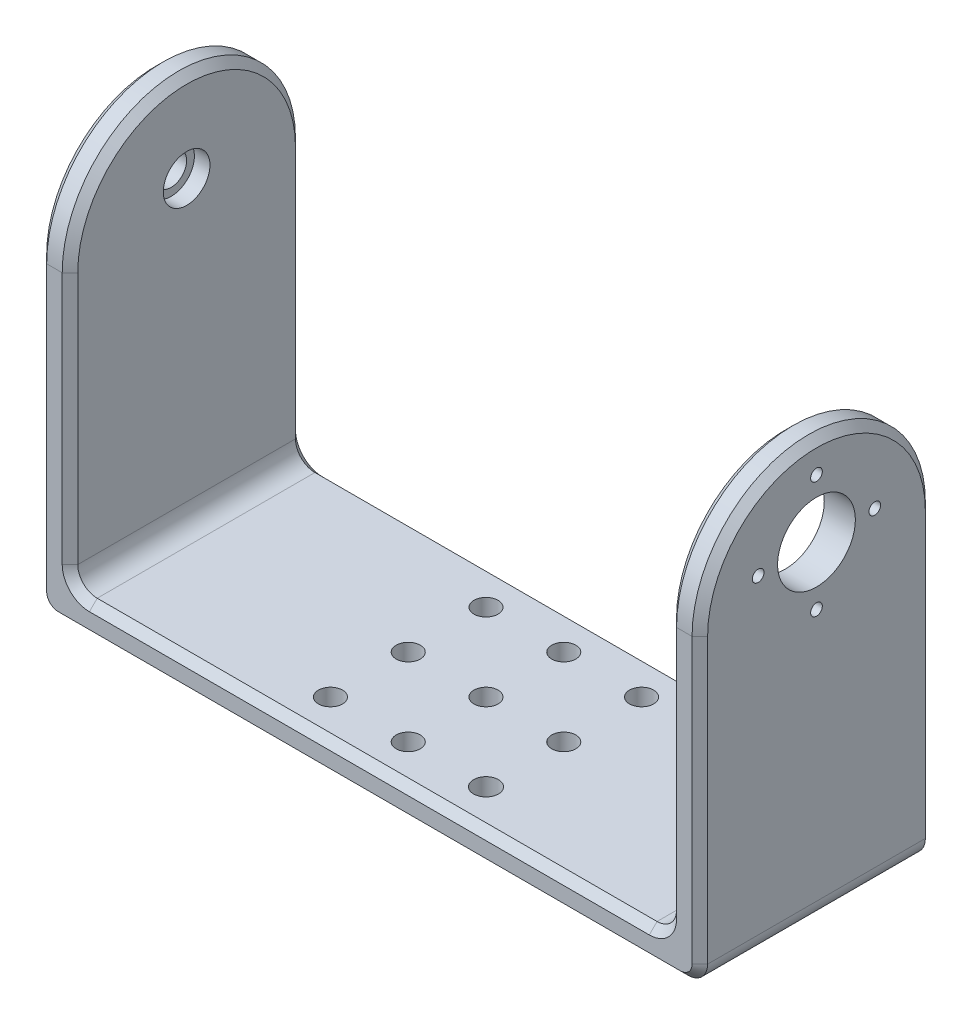
SolidWorks part; units mm, degrees
ref_plane "Front Plane" through (0, 0, 0) normal (0, 0, 1) x (1, 0, 0)
ref_plane "Top Plane" through (0, 0, 0) normal (0, 1, 0) x (1, 0, 0)
ref_plane "Right Plane" through (0, 0, 0) normal (1, 0, 0) x (0, 0, -1)
sketch "Sketch1" plane through (0, 0, 0) normal (0, 1, 0) x (1, 0, 0)
  line L1 (-85, 30) -> (85, 30)
  line L2 (-85, 30) -> (-85, -30)
  line L3 (-85, -30) -> (85, -30)
  line L4 (85, 30) -> (85, -30)
extrude "Boss-Extrude1" add sketch "Sketch1" along normal blind 8
sketch "Sketch2" plane through (0, 8, 0) normal (0, 1, 0) x (1, 0, 0)
  line L1 (-85, 30) -> (-77, 30)
  line L2 (-85, 30) -> (-85, -30)
  line L3 (-85, -30) -> (-77, -30)
  line L4 (-77, 30) -> (-77, -30)
  line L5 (77, 30) -> (77, -30)
  line L6 (85, -30) -> (77, -30)
  line L7 (85, 30) -> (85, -30)
  line L8 (85, 30) -> (77, 30)
extrude "Boss-Extrude2" add sketch "Sketch2" along normal blind 100
sketch "Sketch3" plane through (85, 0, 0) normal (1, 0, 0) x (0, 0, -1)
  circle A0 centre (0, 85) radius 10
  circle A3 centre (0, 70) radius 1.5
  circle A4 centre (0, 100) radius 1.5
  circle A5 centre (-15, 85) radius 1.5
  circle A6 centre (15, 85) radius 1.5
sketch "Sketch4" plane through (-85, 0, 0) normal (-1, 0, 0) x (0, 0, 1)
  circle A0 centre (0, 85) radius 4
extrude "Cut-Extrude1" cut sketch "Sketch3" against normal blind 10
sketch "Sketch5" plane through (-85, 0, 0) normal (-1, 0, 0) x (0, 0, 1)
  circle A0 centre (0, 85) radius 5
extrude "Boss-Extrude3" add sketch "Sketch5" along normal blind 1.5
sketch "Sketch6" plane through (-86.5, 0, 0) normal (-1, 0, 0) x (0, 0, 1)
  circle A0 centre (0, 85) radius 4
extrude "Cut-Extrude3" cut sketch "Sketch6" against normal blind 15
sketch "Sketch7" plane through (-77, 0, 0) normal (1, 0, 0) x (0, 0, -1)
  circle A0 centre (0, 85) radius 6
extrude "Cut-Extrude4" cut sketch "Sketch7" against normal blind 4
fillet "Fillet1" 2 edges at (81, 108, -30) (81, 108, 30) type full round first side face at (0, 56, -30) second side face at (0, 56, 30) middle face at (81, 108, 0)
fillet "Fillet2" 2 edges at (-81, 108, -30) (-81, 108, 30) type full round first side face at (0, 48.5, -30) second side face at (0, 48.5, 30) middle face at (-81, 108, 0)
fillet "Fillet3" radius 5 1 edges at (77, 8, 0) type face fillet first side face at (77, 70, -1.5) second side face at (0, 8, 0)
fillet "Fillet4" radius 5 1 edges at (-77, 8, 0) type face fillet first side face at (-77, 85, -6) second side face at (-2.5, 8, 0)
fillet "Fillet5" radius 5 1 edges at (85, 0, 0) type face fillet first side face at (85, 70, -1.5) second side face at (0, 0, 0)
fillet "Fillet6" radius 5 1 edges at (-85, 0, 0) type face fillet first side face at (-85, 85, -5) second side face at (-2.5, 0, 0)
fillet "Chamfer1" radius 2 24 edges at (85, 108, 0) (77, 108, 0) (-77, 108, 0) (-85, 108, 0) (83.5355, 1.4645, -30) (85, 41.5, -30) (77, 45.5, -30) (75.5355, 9.4645, -30) (0, 8, -30) (-75.5355, 9.4645, -30) (-77, 45.5, -30) (-85, 41.5, -30) (-83.5355, 1.4645, -30) (-77, 45.5, 30) (-75.5355, 9.4645, 30) (0, 8, 30) (75.5355, 9.4645, 30) (77, 45.5, 30) (85, 41.5, 30) (83.5355, 1.4645, 30) (-83.5355, 1.4645, 30) (-85, 41.5, 30) (0, 0, -30) (0, 0, 30) profile chamfer
sketch "Sketch8" plane through (0, 8, 0) normal (0, 1, 0) x (1, 0, 0)
  circle A0 centre (0, 0) radius 3.1
  circle A1 centre (0, 20) radius 3.1
  circle A2 centre (0, -20) radius 3.1
  circle A3 centre (-20, -20) radius 3.1
  circle A4 centre (-20, 20) radius 3.1
  circle A5 centre (-20, 0) radius 3.1
  circle A6 centre (20, -20) radius 3.2
  circle A7 centre (20, 0) radius 3.1
  circle A8 centre (20, 20) radius 3.1
extrude "Cut-Extrude5" cut sketch "Sketch8" against normal blind 10
